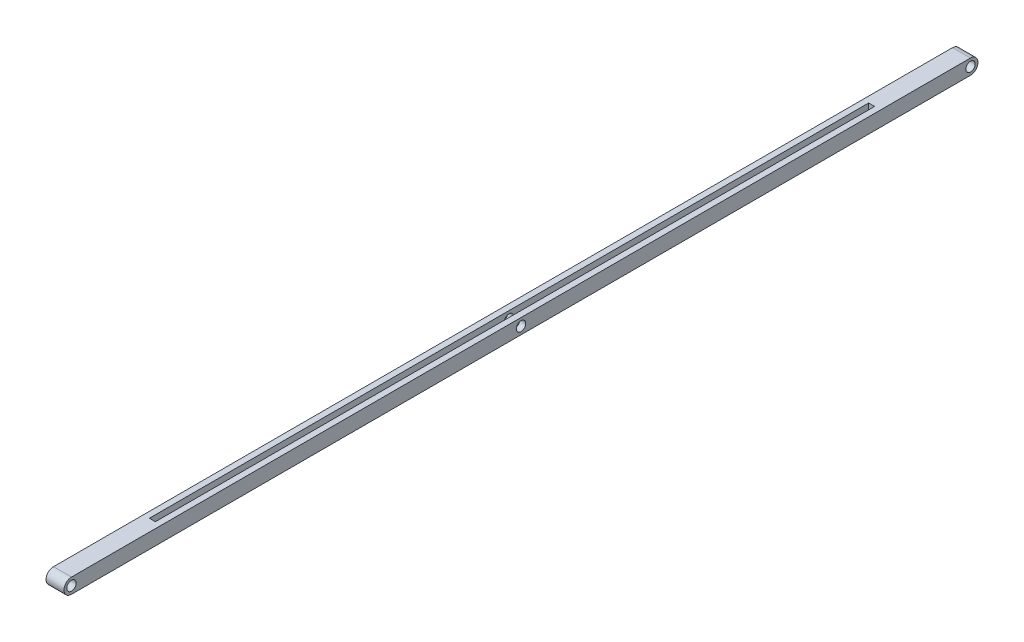
SolidWorks part; units mm, degrees
ref_plane "Front Plane" through (0, 0, 0) normal (0, 0, 1) x (1, 0, 0)
ref_plane "Top Plane" through (0, 0, 0) normal (0, 1, 0) x (1, 0, 0)
ref_plane "Right Plane" through (0, 0, 0) normal (1, 0, 0) x (0, 0, -1)
sketch "Sketch1" plane through (0, 0, 0) normal (1, 0, 0) x (0, 0, -1)
  line L0 (-77.47, 8.4137) -> (684.53, 8.4137)
  line L2 (684.53, -4.2862) -> (-77.47, -4.2863)
  arc A0 (-77.47, -4.2863) -> (-77.47, 8.4137) centre (-77.47, 2.0637) cw
  arc A1 (684.53, -4.2862) -> (684.53, 8.4137) centre (684.53, 2.0638) ccw
  dimension "D1" = 12.7
  dimension "D2" = 762
extrude "Boss-Extrude1" add sketch "Sketch1" along normal blind 15.24
hole_wizard "Ø8.0mm Dowel Hole1" positions "Sketch4" profile "Sketch3" hole size "Ø8.0" standard "ANSI Metric" end condition through all
sketch "Sketch4" plane through (15.24, 0, 0) normal (1, 0, 0) x (0, 0, -1)
  line L1 (303.53, 8.4138) -> (303.53, -4.2862) construction
  line L2 (684.53, 8.4137) -> (-77.47, 8.4137) construction
  line L3 (-77.47, -4.2863) -> (684.53, -4.2862) construction
  arc A0 (-77.47, 8.4137) -> (-77.47, -4.2863) centre (-77.47, 2.0637) ccw construction
  arc A1 (684.53, -4.2862) -> (684.53, 8.4137) centre (684.53, 2.0638) ccw construction
  point P0 (-77.47, 2.0637)
  point P2 (684.53, 2.0638)
  point P12 (303.53, 2.0638)
sketch "Sketch3" plane through (15.24, 2.0637, 77.47) normal (0, 1, 0) x (0, 0, -1)
  line L0 (0, 0) -> (0, 15.24)
  line L1 (0, 15.24) -> (4, 15.24)
  line L2 (4, 15.24) -> (4, 0)
  line L5 (4, 0) -> (0, 0)
  line L11 (0, -6.35) -> (0, 107.95) construction
  dimension "Thru Hole Dia." = 8
  dimension "Thru Hole Depth" = 15.24
sketch "Sketch5" plane through (0, 8.4137, 0) normal (0, 1, 0) x (1, 0, 0)
  line L0 (15.24, 303.53) -> (0, 303.53) construction
  line L1 (5.08, -1.27) -> (10.16, -1.27)
  line L2 (5.08, -1.27) -> (5.08, 608.33)
  line L3 (5.08, 608.33) -> (10.16, 608.33)
  line L4 (10.16, -1.27) -> (10.16, 608.33)
  line L5 (15.24, 684.53) -> (15.24, -77.47) construction
  line L6 (0, 684.53) -> (0, -77.47) construction
  line L7 (7.62, -1.27) -> (7.62, 608.33) construction
  point P10 (10.16, 303.53)
  dimension "D1" = 5.08
  dimension "D2" = 609.6
extrude "Cut-Extrude1" cut sketch "Sketch5" against normal through all
